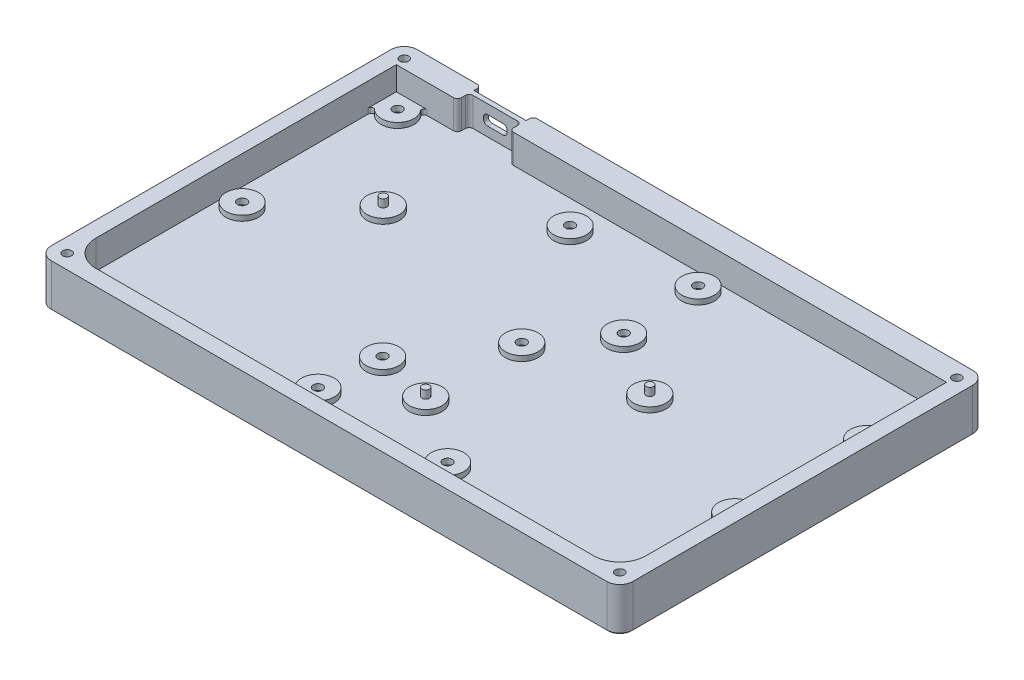
SolidWorks part; units mm, degrees
ref_plane "Front Plane" through (0, 0, 0) normal (0, 0, 1) x (1, 0, 0)
ref_plane "Top Plane" through (0, 0, 0) normal (0, 1, 0) x (1, 0, 0)
ref_plane "Right Plane" through (0, 0, 0) normal (1, 0, 0) x (0, 0, -1)
sketch "Sketch1" plane through (0, 0, 0) normal (0, 1, 0) x (1, 0, 0)
  line L1 (0, 0) -> (222.53, 0)
  line L2 (0, 0) -> (0, 140)
  line L3 (0, 140) -> (222.53, 140)
  line L4 (222.53, 0) -> (222.53, 140)
  dimension "D1" = 140
  dimension "D2" = 222.53
extrude "Baseplate" add sketch "Sketch1" along normal blind 5.6
sketch "Sketch2" plane through (0, 5.6, 0) normal (0, 1, 0) x (1, 0, 0)
  line L1 (0, 140) -> (222.53, 140)
  line L2 (0, 140) -> (0, 0)
  line L3 (0, 0) -> (222.53, 0)
  line L4 (222.53, 140) -> (222.53, 0)
  line L5 (206.53, 6) -> (16, 6)
  line L6 (216.53, 16) -> (216.53, 131)
  line L7 (216.53, 131) -> (6, 131)
  line L8 (6, 16) -> (6, 131)
  arc A0 (206.53, 6) -> (216.53, 16) centre (206.53, 16) ccw
  arc A1 (16, 6) -> (6, 16) centre (16, 16) cw
  dimension "D5" = 10
  dimension "D1" = 6
  dimension "D2" = 6
  dimension "D3" = 6
  dimension "D4" = 9
extrude "Sidewalls" add sketch "Sketch2" along normal blind 11
sketch "Sketch3" plane through (0, 16.6, 0) normal (0, 1, 0) x (1, 0, 0)
  line L0 (216.53, 131) -> (6, 131) construction
  line L1 (29.38, 131) -> (49.38, 131)
  line L2 (29.38, 131) -> (29.38, 135.5)
  line L3 (29.38, 135.5) -> (49.38, 135.5)
  line L4 (49.38, 131) -> (49.38, 135.5)
  line L5 (0, 140) -> (0, 0) construction
  line L7 (39.38, 135.5) -> (39.38, 131) construction
  point P8 (0, 0)
  point P9 (0, 0)
  dimension "D1" = 20
  dimension "D2" = 4.5
  dimension "D3" = 39.38
extrude "USB Relief" cut sketch "Sketch3" against normal up to surface (11 mm away) up to face at (111.265, 5.6, -50.3096)
sketch "Sketch6" plane through (0, 5.6, 0) normal (0, 1, 0) x (1, 0, 0)
  circle A0 centre (12, 125.5) radius 6.25
  circle A1 centre (83.5, 120) radius 6.25
  circle A2 centre (41, 91) radius 6.25
  circle A3 centre (13, 65) radius 6.25
  circle A4 centre (91, 40.75) radius 6.25
  circle A5 centre (138.5, 18.125) radius 6.25
  circle A6 centre (89, 18) radius 6.25
  circle A7 centre (112.5, 35.75) radius 6.25
  circle A8 centre (113, 72) radius 6.25
  circle A9 centre (210, 56.5) radius 6.25
  circle A10 centre (154.5, 79.5) radius 6.25
  circle A11 centre (211, 106) radius 6.25
  circle A12 centre (128, 124.5) radius 6.25
  circle A13 centre (129.5, 94.5) radius 6.25
  point P42 (12, 125.5)
  point P44 (41, 91)
  point P46 (83.5, 120)
  point P48 (13, 65)
  point P50 (128, 124.5)
  point P52 (129.5, 94.5)
  point P54 (113, 72)
  point P56 (91, 40.75)
  point P58 (89, 18)
  point P60 (112.5, 35.75)
  point P62 (138.5, 18.125)
  point P64 (210, 56.5)
  point P66 (154.5, 79.5)
  point P68 (211, 106)
  dimension "D1" = 12.5
extrude "PCB Support" add sketch "Sketch6" along normal blind 2
sketch "Sketch15" plane through (0, 5.6, 0) normal (0, 1, 0) x (1, 0, 0)
  line L1 (6, 131) -> (12, 131)
  line L2 (6, 131) -> (6, 125.5)
  line L3 (6, 125.5) -> (12, 125.5)
  line L4 (12, 131) -> (12, 125.5)
  arc A0 (6, 123.75) -> (14.9686, 131) centre (12, 125.5) ccw construction
extrude "Corner Fill" add sketch "Sketch15" along normal up to vertex (2 mm away) up to point (6, 7.6, -123.75)
fillet "Fillet3" radius 1 2 edges at (6, 6.6, -123.75) (14.9686, 6.6, -131)
sketch "Sketch4" plane through (0, 5.6, 0) normal (0, 1, 0) x (1, 0, 0)
  line L1 (9.1, 128.4) -> (14.9, 128.4)
  line L2 (9.1, 128.4) -> (9.1, 122.6)
  line L3 (9.1, 122.6) -> (14.9, 122.6)
  line L4 (14.9, 128.4) -> (14.9, 122.6)
  line L5 (9.1, 128.4) -> (14.9, 122.6) construction
  line L6 (9.1, 122.6) -> (14.9, 128.4) construction
  line L7 (80.6, 122.9) -> (86.4, 122.9)
  line L8 (80.6, 122.9) -> (80.6, 117.1)
  line L9 (80.6, 117.1) -> (86.4, 117.1)
  line L10 (86.4, 122.9) -> (86.4, 117.1)
  line L11 (80.6, 122.9) -> (86.4, 117.1) construction
  line L12 (80.6, 117.1) -> (86.4, 122.9) construction
  line L13 (10.1, 62.1) -> (15.9, 62.1)
  line L14 (10.1, 62.1) -> (10.1, 67.9)
  line L15 (10.1, 67.9) -> (15.9, 67.9)
  line L16 (15.9, 62.1) -> (15.9, 67.9)
  line L17 (10.1, 62.1) -> (15.9, 67.9) construction
  line L18 (10.1, 67.9) -> (15.9, 62.1) construction
  line L19 (88.1, 37.85) -> (93.9, 37.85)
  line L20 (88.1, 37.85) -> (88.1, 43.65)
  line L21 (88.1, 43.65) -> (93.9, 43.65)
  line L22 (93.9, 37.85) -> (93.9, 43.65)
  line L23 (88.1, 37.85) -> (93.9, 43.65) construction
  line L24 (88.1, 43.65) -> (93.9, 37.85) construction
  line L25 (110.1, 69.1) -> (115.9, 69.1)
  line L26 (110.1, 69.1) -> (110.1, 74.9)
  line L27 (110.1, 74.9) -> (115.9, 74.9)
  line L28 (115.9, 69.1) -> (115.9, 74.9)
  line L29 (110.1, 69.1) -> (115.9, 74.9) construction
  line L30 (110.1, 74.9) -> (115.9, 69.1) construction
  line L31 (135.6, 15.225) -> (141.4, 15.225)
  line L32 (135.6, 15.225) -> (135.6, 21.025)
  line L33 (135.6, 21.025) -> (141.4, 21.025)
  line L34 (141.4, 15.225) -> (141.4, 21.025)
  line L35 (135.6, 15.225) -> (141.4, 21.025) construction
  line L36 (135.6, 21.025) -> (141.4, 15.225) construction
  line L37 (91.9, 15.1) -> (86.1, 15.1)
  line L38 (91.9, 15.1) -> (91.9, 20.9)
  line L39 (91.9, 20.9) -> (86.1, 20.9)
  line L40 (86.1, 15.1) -> (86.1, 20.9)
  line L41 (91.9, 15.1) -> (86.1, 20.9) construction
  line L42 (91.9, 20.9) -> (86.1, 15.1) construction
  line L43 (212.9, 59.4) -> (207.1, 59.4)
  line L44 (212.9, 59.4) -> (212.9, 53.6)
  line L45 (212.9, 53.6) -> (207.1, 53.6)
  line L46 (207.1, 59.4) -> (207.1, 53.6)
  line L47 (212.9, 59.4) -> (207.1, 53.6) construction
  line L48 (212.9, 53.6) -> (207.1, 59.4) construction
  line L49 (126.6, 91.6) -> (132.4, 91.6)
  line L50 (126.6, 91.6) -> (126.6, 97.4)
  line L51 (126.6, 97.4) -> (132.4, 97.4)
  line L52 (132.4, 91.6) -> (132.4, 97.4)
  line L53 (126.6, 91.6) -> (132.4, 97.4) construction
  line L54 (126.6, 97.4) -> (132.4, 91.6) construction
  line L55 (125.1, 127.4) -> (130.9, 127.4)
  line L56 (125.1, 127.4) -> (125.1, 121.6)
  line L57 (125.1, 121.6) -> (130.9, 121.6)
  line L58 (130.9, 127.4) -> (130.9, 121.6)
  line L59 (125.1, 127.4) -> (130.9, 121.6) construction
  line L60 (125.1, 121.6) -> (130.9, 127.4) construction
  line L61 (213.9, 103.1) -> (208.1, 103.1)
  line L62 (213.9, 103.1) -> (213.9, 108.9)
  line L63 (213.9, 108.9) -> (208.1, 108.9)
  line L64 (208.1, 103.1) -> (208.1, 108.9)
  line L65 (213.9, 103.1) -> (208.1, 108.9) construction
  line L66 (213.9, 108.9) -> (208.1, 103.1) construction
  point P0 (12, 125.5)
  point P6 (83.5, 120)
  point P12 (13, 65)
  point P18 (91, 40.75)
  point P24 (113, 72)
  point P30 (138.5, 18.125)
  point P36 (89, 18)
  point P42 (210, 56.5)
  point P48 (129.5, 94.5)
  point P54 (128, 124.5)
  point P60 (211, 106)
  dimension "D1" = 5.8
extrude "Nut Cutout" cut sketch "Sketch4" against normal blind 1.8 from offset 0.2 offset against normal yes
sketch "Sketch7" plane through (0, 7.6, 0) normal (0, 1, 0) x (1, 0, 0)
  circle A0 centre (41, 91) radius 1.4
  circle A1 centre (154.5, 79.5) radius 1.4
  circle A2 centre (112.5, 35.75) radius 1.4
  dimension "D1" = 2.8
extrude "Alignment Pins" add sketch "Sketch7" along normal blind 3
sketch "Sketch8" plane through (0, 0, -135.5) normal (0, 0, 1) x (1, 0, 0)
  line L1 (29.38, 5.6) -> (49.38, 5.6)
  line L2 (29.38, 5.6) -> (29.38, 16.6)
  line L3 (29.38, 16.6) -> (49.38, 16.6)
  line L4 (49.38, 5.6) -> (49.38, 16.6)
extrude "Thin USB Wall" cut sketch "Sketch8" against normal up to next from offset 1.8 offset against normal yes
hole_wizard "M3 Clearance Hole1" positions "3DSketch1" profile "Sketch9" hole size "M3" standard "ANSI Metric"
sketch3d "3DSketch1"
  line L0 (12, 7.6, -125.5) -> (12, 5.6, -125.5) construction
  line L5 (113, 7.6, -72) -> (113, 5.6, -72) construction
  line L7 (91, 7.6, -40.75) -> (91, 5.6, -40.75) construction
  line L8 (89, 7.6, -18) -> (89, 5.6, -18) construction
  line L9 (138.5, 7.6, -18.125) -> (138.5, 5.6, -18.125) construction
  line L10 (210, 7.6, -56.5) -> (210, 5.6, -56.5) construction
  line L11 (83.5, 7.6, -120) -> (83.5, 5.6, -120) construction
  line L12 (128, 7.6, -124.5) -> (128, 5.6, -124.5) construction
  line L13 (211, 7.6, -106) -> (211, 5.6, -106) construction
  line L14 (129.5, 7.6, -94.5) -> (129.5, 5.6, -94.5) construction
  line L15 (13, 7.6, -65) -> (13, 5.6, -65) construction
  point P44 (12, 7.6, -125.5)
  point P64 (113, 7.6, -72)
  point P72 (91, 7.6, -40.75)
  point P76 (89, 7.6, -18)
  point P80 (138.5, 7.6, -18.125)
  point P84 (210, 7.6, -56.5)
  point P92 (83.5, 7.6, -120)
  point P96 (128, 7.6, -124.5)
  point P100 (211, 7.6, -106)
  point P104 (129.5, 7.6, -94.5)
  point P108 (13, 7.6, -65)
sketch "Sketch9" plane through (12, 7.6, -125.5) normal (1, 0, 0) x (0, 0, 1)
  line L0 (0, 0) -> (0, 3.5)
  line L1 (0, 3.5) -> (1.8, 2.4185)
  line L2 (1.8, 2.4185) -> (1.8, 0)
  line L5 (1.8, 0) -> (0, 0)
  line L10 (0, 3.5) -> (-1.8, 2.4185) construction
  line L11 (0, -6.35) -> (0, 107.95) construction
  dimension "Hole Dia." = 3.6
  dimension "Hole Depth" = 3.5
  dimension "Drill Angle" = 118
hole_wizard "CSK for M3 Flat Head Machine Screw1" positions "3DSketch2" profile "Sketch11" countersink size "M3" standard "ANSI Metric" end condition through all
sketch3d "3DSketch2"
  line L1 (0, 0, -140) -> (0, 0, 0) construction
  line L2 (222.53, 0, -140) -> (0, 0, -140) construction
  line L3 (0, 0, 0) -> (222.53, 0, 0) construction
  line L4 (222.53, 0, 0) -> (222.53, 0, -140) construction
  point P0 (217.03, 0, -5.5)
  point P2 (5.5, 0, -5.5)
  point P4 (5.5, 0, -134.5)
  point P6 (217.03, 0, -134.5)
  dimension "D1" = 5.5
  dimension "D2" = 5.5
  dimension "D3" = 5.5
  dimension "D4" = 5.5
  dimension "D5" = 5.5
  dimension "D6" = 5.5
  dimension "D7" = 5.5
  dimension "D8" = 5.5
sketch "Sketch11" plane through (217.03, 0, -5.5) normal (1, 0, 0) x (0, 0, -1)
  line L0 (0, 0) -> (0, 16.6)
  line L1 (0, 16.6) -> (1.7, 16.6)
  line L2 (1.7, 16.6) -> (1.7, 1.45)
  line L3 (1.7, 1.45) -> (3.15, 0)
  line L5 (3.15, 0) -> (0, 0)
  line L6 (-1.7, 1.45) -> (-3.15, 0) construction
  line L11 (0, -6.35) -> (0, 107.95) construction
  dimension "Thru Hole Dia." = 3.4
  dimension "Thru Hole Depth" = 16.6
  dimension "Near C'Sink Dia." = 6.3
  dimension "Near C'Sink Angle" = 90
sketch "Sketch12" plane through (0, 0, -137.3) normal (0, 0, -1) x (-1, 0, 0)
  line L0 (-39.38, 13) -> (-39.38, 16.6) construction
  line L1 (-42.38, 13) -> (-36.38, 13)
  line L2 (-43.88, 11.5) -> (-43.88, 10.7)
  line L3 (-42.38, 9.2) -> (-36.38, 9.2)
  line L4 (-34.88, 11.5) -> (-34.88, 10.7)
  line L5 (-49.38, 16.6) -> (-29.38, 16.6) construction
  arc A0 (-36.38, 9.2) -> (-34.88, 10.7) centre (-36.38, 10.7) ccw
  arc A1 (-43.88, 10.7) -> (-42.38, 9.2) centre (-42.38, 10.7) ccw
  arc A2 (-42.38, 13) -> (-43.88, 11.5) centre (-42.38, 11.5) ccw
  arc A3 (-36.38, 13) -> (-34.88, 11.5) centre (-36.38, 11.5) cw
  dimension "D1" = 1.5
  dimension "D2" = 9
  dimension "D3" = 3.8
  dimension "D4" = 3.6
extrude "USB Port" cut sketch "Sketch12" against normal up to next
fillet "Fillet1" radius 5 4 edges at (222.53, 8.3, -140) (222.53, 8.3, 0) (0, 8.3, 0) (0, 8.3, -140)
fillet "Fillet2" radius 1.5 6 edges at (29.38, 11.1, -135.5) (49.38, 11.1, -135.5) (29.38, 11.1, -131) (49.38, 11.1, -131) (49.38, 11.1, -140) (29.38, 11.1, -140)
sketch "Sketch13" plane through (0, 0, 0) normal (0, -1, 0) x (1, 0, 0)
  line L1 (11.265, -130) -> (211.265, -130)
  line L2 (11.265, -130) -> (11.265, -10)
  line L3 (11.265, -10) -> (211.265, -10)
  line L4 (211.265, -130) -> (211.265, -10)
  line L8 (0, 0) -> (222.53, 0) construction
  line L9 (111.265, 0) -> (111.265, -10) construction
  line L10 (11.265, -70) -> (0, -70) construction
  line L11 (0, 0) -> (0, -140) construction
  dimension "D1" = 120
  dimension "D2" = 200
extrude "Cut-Extrude1" cut sketch "Sketch13" against normal blind 2.6
chamfer "Chamfer1" distance 0.5 angle 45 12 edges at (0, 0, -70) (1.4645, 0, -1.4645) (1.4645, 0, -138.5355) (111.265, 0, 0) (111.265, 0, -140) (221.0655, 0, -1.4645) (221.0655, 0, -138.5355) (222.53, 0, -70) (111.265, 0, -130) (211.265, 0, -70) (111.265, 0, -10) (11.265, 0, -70)
sketch "Sketch14" [suppressed] plane through (0, 0, 0) normal (0, -1, 0) x (1, 0, 0)
  line L0 (0, -5) -> (0, 22.5054)
  line L1 (3, 11.9698) -> (3, -0.4174)
  line L2 (111.265, 0) -> (111.265, -140) construction
  line L3 (5, 0) -> (217.53, 0) construction
  line L4 (217.53, -140) -> (5, -140) construction
  line L5 (0, -70) -> (222.53, -70) construction
  line L6 (0, -135) -> (0, -5) construction
  line L7 (222.53, -5) -> (222.53, -135) construction
  line L8 (219.53, 11.9698) -> (219.53, -0.4174)
  line L9 (222.53, -5) -> (222.53, 22.5054)
  line L10 (222.53, -135) -> (222.53, -162.5054)
  line L11 (219.53, -151.9698) -> (219.53, -139.5826)
  line L12 (3, -151.9698) -> (3, -139.5826)
  line L13 (0, -135) -> (0, -162.5054)
  line L14 (3, -0.4174) -> (0, -5)
  line L15 (219.53, -0.4174) -> (222.53, -5)
  line L16 (222.53, -135) -> (219.53, -139.5826)
  line L17 (0, -135) -> (3, -139.5826)
  arc A0 (5, 0) -> (0, -5) centre (5, -5) ccw construction
  circle A1 centre (20, 22.5054) radius 20
  circle A2 centre (202.53, 22.5054) radius 20
  circle A3 centre (202.53, -162.5054) radius 20
  circle A4 centre (20, -162.5054) radius 20
  dimension "D2" = 40
  dimension "D1" = 3
extrude "Boss-Extrude1" [suppressed] add sketch "Sketch14" against normal blind 1
